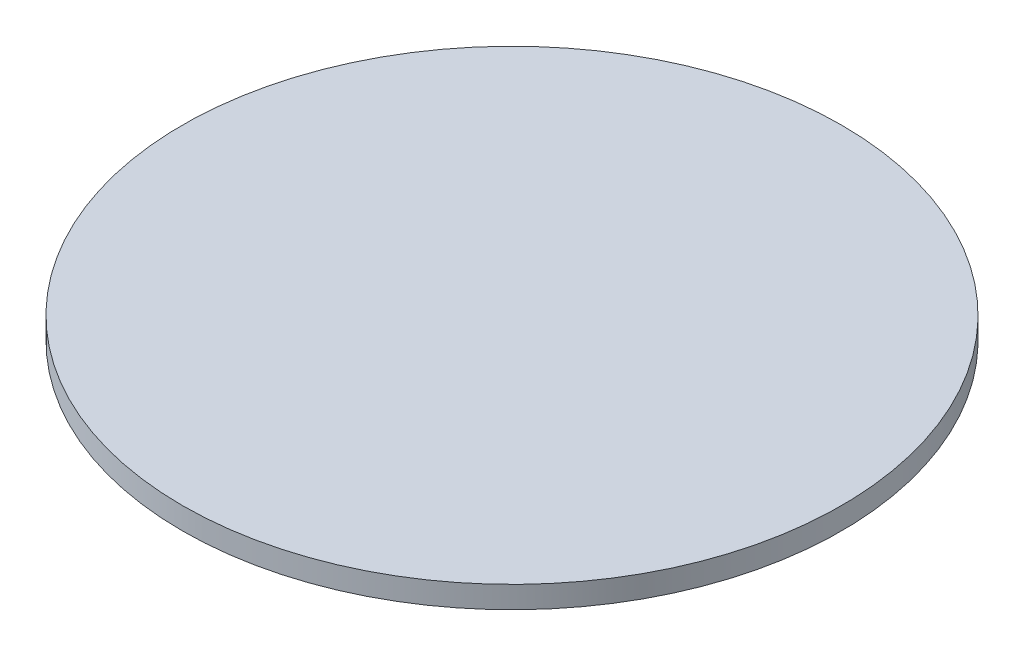
SolidWorks part; units mm, degrees
material "A-Glass Fiber"
ref_plane "Front Plane" through (0, 0, 0) normal (0, 0, 1) x (1, 0, 0)
ref_plane "Top Plane" through (0, 0, 0) normal (0, 1, 0) x (1, 0, 0)
ref_plane "Right Plane" through (0, 0, 0) normal (1, 0, 0) x (0, 0, -1)
sketch "Sketch1" plane through (0, 0, 0) normal (0, 1, 0) x (1, 0, 0)
  circle A0 centre (0, 0) radius 47.625
  dimension "D1" = 95.25
extrude "Boss-Extrude1" add sketch "Sketch1" along normal blind 3.175
